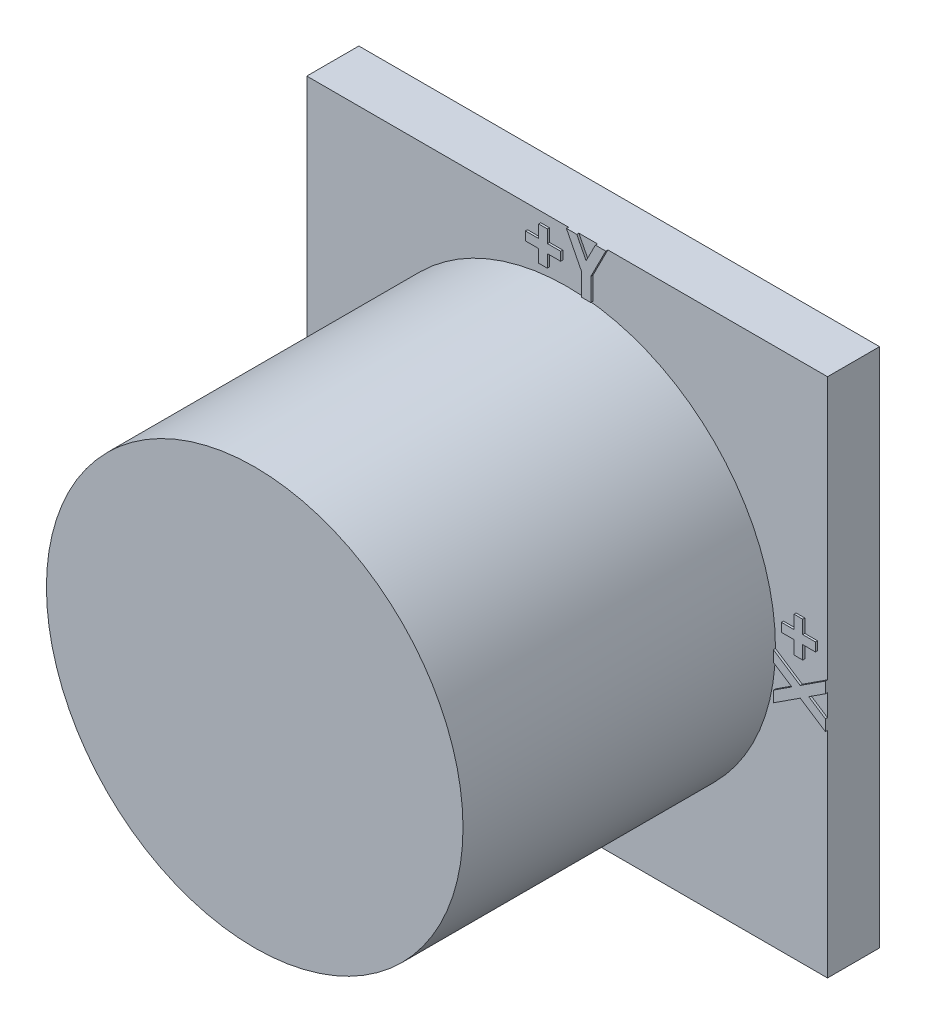
SolidWorks part; units mm, degrees
ref_plane "Front Plane" through (0, 0, 0) normal (0, 0, 1) x (1, 0, 0)
ref_plane "Top Plane" through (0, 0, 0) normal (0, 1, 0) x (1, 0, 0)
ref_plane "Right Plane" through (0, 0, 0) normal (1, 0, 0) x (0, 0, -1)
sketch "Sketch3" plane through (0, 0, 0) normal (0, 0, 1) x (1, 0, 0)
  line L1 (-250, -250) -> (250, -250)
  line L2 (-250, -250) -> (-250, 250)
  line L3 (-250, 250) -> (250, 250)
  line L4 (250, -250) -> (250, 250)
  line L5 (-250, -250) -> (250, 250) construction
  line L6 (-250, 250) -> (250, -250) construction
  circle A0 centre (0, 0) radius 200
  dimension "D1" = 400
  dimension "D2" = 500
extrude "Boss-Extrude3" add sketch "Sketch3" against normal blind 300 contours A0 region at (0, 0, 0)
extrude "Boss-Extrude4" add sketch "Sketch3<3>" against normal blind 50 from surface contours L2 L3 L4 L1 starting at face at (200, 0, -300)
sketch "Sketch3<3>" plane through (0, 0, 0) normal (0, 0, 1) x (1, 0, 0) same geometry as "Sketch3"
sketch "Sketch4" plane through (0, 0, -300) normal (0, 0, 1) x (1, 0, 0)
  line L0 (200, 250) -> (200, -250) construction
  line L1 (-250, 250) -> (250, 250) construction
  line L2 (-250, -250) -> (250, -250) construction
  line L3 (-250, 200) -> (250, 200) construction
  line L4 (-250, -250) -> (-250, 250) construction
  line L5 (250, -250) -> (250, 250) construction
  text T0 "<b>+X</b>" font "Century Gothic" height 50
  text T1 "<b>+Y</b>" font "Century Gothic" height 50
  text T2 "<b>-X</b>" font "Century Gothic" height 49
  text T3 "<b>-Y</b>" font "Century Gothic" height 49
  dimension "D1" = 50
  dimension "D2" = 50
extrude "Boss-Extrude5" add sketch "Sketch4" along normal blind 2
ref_plane "Plane1" through (0, 0, 400) normal (0, 0, 1) x (1, 0, 0)
